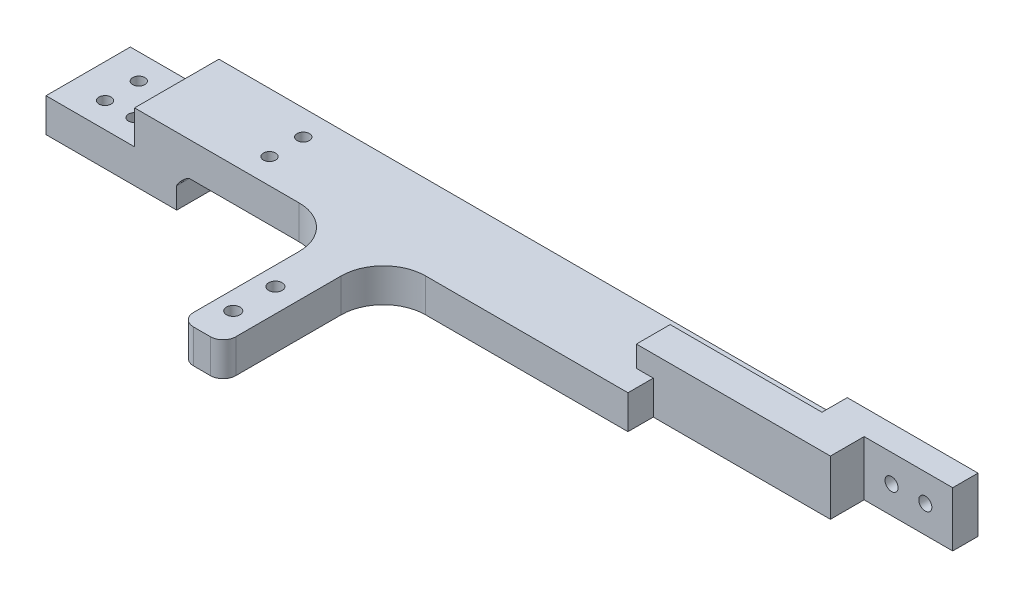
SolidWorks part; units mm, degrees
ref_plane "Front" through (0, 0, 0) normal (0, 0, 1) x (1, 0, 0)
ref_plane "Top" through (0, 0, 0) normal (0, 1, 0) x (1, 0, 0)
ref_plane "Right" through (0, 0, 0) normal (1, 0, 0) x (0, 0, -1)
sketch "Sketch1" plane through (0, 0, 0) normal (0, 1, 0) x (1, 0, 0)
  line L1 (0, 0) -> (300, 0)
  line L2 (0, 0) -> (0, -20)
  line L3 (0, -20) -> (300, -20)
  line L4 (300, 0) -> (300, -20)
  dimension "D1" = 20
  dimension "D2" = 300
extrude "Boss-Extrude1" add sketch "Sketch1" along normal blind 8
sketch "Sketch2" plane through (0, 0, 20) normal (0, 0, 1) x (1, 0, 0)
  line L0 (0, 8) -> (300, 8) construction
  line L1 (0, 0) -> (34, 0)
  line L2 (0, 0) -> (0, 8)
  line L3 (0, 8) -> (34, 8)
  line L4 (34, 0) -> (34, 8)
  line L5 (266, 8) -> (300, 8)
  line L6 (300, 0) -> (300, 8)
  line L7 (266, 0) -> (300, 0)
  line L8 (266, 0) -> (266, 8)
  dimension "D1" = 34
  dimension "D2" = 2
extrude "Boss-Extrude2" add sketch "Sketch2" along normal blind 9
sketch "Sketch3" plane through (0, 0, 0) normal (0, 0, -1) x (-1, 0, 0)
  line L0 (-300, 8) -> (0, 8) construction
  line L1 (0, 0) -> (-34, 0)
  line L2 (0, 0) -> (0, 8)
  line L3 (0, 8) -> (-34, 8)
  line L4 (-34, 0) -> (-34, 8)
  line L5 (-300, 0) -> (-300, 8)
  line L6 (-266, 8) -> (-300, 8)
  line L7 (-266, 0) -> (-266, 8)
  line L8 (-266, 0) -> (-300, 0)
  dimension "D1" = 34
  dimension "D2" = 2
extrude "Boss-Extrude3" add sketch "Sketch3" along normal blind 9
sketch "Sketch4" plane through (0, 8, 0) normal (0, 1, 0) x (1, 0, 0)
  line L0 (0, 9) -> (34, 9) construction
  line L1 (0, 9) -> (0, -29) construction
  circle A0 centre (4, 5) radius 1.45
  circle A1 centre (30, 5) radius 1.45
  circle A2 centre (30, -25) radius 1.45
  circle A3 centre (4, -25) radius 1.45
  circle A4 centre (296, -25) radius 1.45
  circle A5 centre (296, 5) radius 1.45
  circle A6 centre (270, -25) radius 1.45
  circle A7 centre (270, 5) radius 1.45
  dimension "D1" = 2.9
  dimension "D2" = 4
  dimension "D3" = 4
  dimension "D4" = 2
  dimension "D5" = 2
  dimension "D6" = 2
extrude "Cut-Extrude1" cut sketch "Sketch4" against normal through all
sketch "Sketch5" plane through (0, 0, 20) normal (0, 0, 1) x (1, 0, 0)
  line L0 (34, 8) -> (266, 8) construction
  line L1 (266, 0) -> (241, 0)
  line L2 (266, 0) -> (266, 8)
  line L3 (266, 8) -> (241, 8)
  line L4 (241, 0) -> (241, 8)
  dimension "D1" = 25
extrude "Boss-Extrude4" add sketch "Sketch5" along normal blind 17
sketch "Sketch6" plane through (0, 0, 0) normal (0, 0, -1) x (-1, 0, 0)
  line L0 (-266, 0) -> (-34, 0) construction
  line L1 (-266, 8) -> (-241, 8)
  line L2 (-266, 8) -> (-266, 0)
  line L3 (-266, 0) -> (-241, 0)
  line L4 (-241, 8) -> (-241, 0)
  dimension "D1" = 25
extrude "Boss-Extrude5" add sketch "Sketch6" along normal blind 17
sketch "Sketch12" plane through (0, 0, 37) normal (0, 0, 1) x (1, 0, 0)
  line L0 (241, 0) -> (266, 0) construction
  line L1 (241, 8) -> (249, 8)
  line L2 (241, 8) -> (241, 0)
  line L3 (241, 0) -> (249, 0)
  line L4 (249, 8) -> (249, 0)
  dimension "D1" = 8
extrude "Boss-Extrude7" add sketch "Sketch12" along normal blind 17
sketch "Sketch14" plane through (0, 0, 29) normal (0, 0, 1) x (1, 0, 0)
  line L0 (300, 8) -> (266, 8) construction
  line L1 (294.975, 8) -> (275, 8)
  line L2 (294.975, 8) -> (294.975, -5)
  line L3 (294.975, -5) -> (275, -4)
  line L4 (275, 8) -> (275, -4)
  line L7 (266, 8) -> (266, 0) construction
  dimension "D1" = 20
  dimension "D2" = 9
  dimension "D3" = 13
  dimension "D4" = 12
extrude "Boss-Extrude8" add sketch "Sketch14" along normal blind 12
sketch "Sketch15" plane through (294.975, 0, 0) normal (1, 0, 0) x (0, 0, -1)
  line L0 (-41, -5) -> (-41, 8) construction
  line L2 (-41, -5) -> (-29, -5) construction
  circle A0 centre (-35, 0) radius 1.6
  dimension "D1" = 3.2
  dimension "D2" = 6
  dimension "D3" = 5
extrude "Cut-Extrude7" cut sketch "Sketch15" against normal blind 20
sketch "Sketch16" plane through (0, 0, -9) normal (0, 0, -1) x (-1, 0, 0)
  line L0 (-266, 8) -> (-300, 8) construction
  line L1 (-295, 8) -> (-275, 8)
  line L2 (-295, 8) -> (-295, -5)
  line L3 (-295, -5) -> (-275, -5)
  line L4 (-275, 8) -> (-275, -5)
  line L6 (-266, 0) -> (-266, 8) construction
  dimension "D1" = 20
  dimension "D2" = 9
  dimension "D3" = 13
extrude "Boss-Extrude9" add sketch "Sketch16" along normal blind 12
sketch "Sketch17" plane through (295, 0, 0) normal (1, 0, 0) x (0, 0, -1)
  line L0 (21, -5) -> (9, -5) construction
  line L1 (21, 8) -> (21, -5) construction
  circle A0 centre (15, 0) radius 1.6
  dimension "D1" = 3.2
  dimension "D2" = 5
  dimension "D3" = 6
extrude "Cut-Extrude8" cut sketch "Sketch17" against normal blind 20
sketch "Sketch18" plane through (0, 0, -9) normal (0, 0, -1) x (-1, 0, 0)
  line L0 (0, 8) -> (-34, 8) construction
  line L1 (-25, 8) -> (-5, 8)
  line L2 (-25, 8) -> (-25, -5)
  line L3 (-25, -5) -> (-5, -5)
  line L4 (-5, 8) -> (-5, -5)
  line L6 (-34, 8) -> (-34, 0) construction
  dimension "D1" = 20
  dimension "D2" = 9
  dimension "D3" = 13
extrude "Boss-Extrude10" add sketch "Sketch18" along normal blind 12
sketch "Sketch19" plane through (5, 0, 0) normal (-1, 0, 0) x (0, 0, 1)
  line L0 (-21, -5) -> (-21, 8) construction
  line L2 (-21, -5) -> (-9, -5) construction
  circle A0 centre (-15, 0) radius 1.6
  dimension "D1" = 3.2
  dimension "D2" = 6
  dimension "D3" = 5
extrude "Cut-Extrude9" cut sketch "Sketch19" against normal blind 20
sketch "Sketch20" plane through (0, 0, 29) normal (0, 0, 1) x (1, 0, 0)
  line L0 (34, 8) -> (0, 8) construction
  line L1 (5, 8) -> (25, 8)
  line L2 (5, 8) -> (5, -5)
  line L3 (5, -5) -> (25, -5)
  line L4 (25, 8) -> (25, -5)
  line L6 (34, 0) -> (34, 8) construction
  dimension "D1" = 20
  dimension "D2" = 9
  dimension "D3" = 13
extrude "Boss-Extrude11" add sketch "Sketch20" along normal blind 12
sketch "Sketch21" plane through (5, 0, 0) normal (-1, 0, 0) x (0, 0, 1)
  line L0 (41, 8) -> (41, -5) construction
  line L1 (41, -5) -> (29, -5) construction
  circle A0 centre (35, 0) radius 1.6
  dimension "D1" = 3.2
  dimension "D2" = 6
  dimension "D3" = 5
extrude "Cut-Extrude10" cut sketch "Sketch21" against normal blind 20
sketch "Sketch22" plane through (0, 8, 0) normal (0, 1, 0) x (1, 0, 0)
  line L0 (241, 17) -> (241, 0) construction
  line L1 (259, 9) -> (249, 9)
  line L2 (259, 9) -> (259, -29)
  line L3 (259, -29) -> (249, -29)
  line L4 (249, 9) -> (249, -29)
  line L5 (241, 17) -> (266, 17) construction
  line L6 (266, -37) -> (249, -37) construction
  dimension "D1" = 8
  dimension "D2" = 10
  dimension "D3" = 8
  dimension "D4" = 8
extrude "Cut-Extrude11" cut sketch "Sketch22" against normal through all
sketch "Sketch23" plane through (0, 0, 0) normal (0, -1, 0) x (-1, 0, 0)
  line L0 (-259, -29) -> (-259, 9) construction
  line L1 (-259, -19) -> (-267, -19)
  line L2 (-259, -19) -> (-259, -1)
  line L3 (-259, -1) -> (-267, -1)
  line L4 (-267, -19) -> (-267, -1)
  line L5 (-249, -29) -> (-259, -29) construction
  dimension "D1" = 8
  dimension "D2" = 10
  dimension "D3" = 10
extrude "Cut-Extrude12" cut sketch "Sketch23" against normal blind 4
sketch "Sketch24" plane through (259, 0, 0) normal (-1, 0, 0) x (0, 0, 1)
  line L0 (-9, 0) -> (-9, 8)
  line L1 (-9, 8) -> (-1, 8)
  line L2 (29, 8) -> (-9, 8) construction
  line L3 (-1, 8) -> (-9, 0)
  line L4 (29, 0) -> (29, 8)
  line L5 (29, 8) -> (21, 8)
  line L6 (21, 8) -> (29, 0)
  dimension "D1" = 8
  dimension "D2" = 8
extrude "Boss-Extrude12" add sketch "Sketch24" along normal blind 10
sketch "Sketch25" plane through (267, 0, 0) normal (-1, 0, 0) x (0, 0, 1)
  line L0 (19, 0) -> (19, 4)
  line L1 (19, 4) -> (15, 4)
  line L2 (1, 4) -> (19, 4) construction
  line L3 (15, 4) -> (19, 0)
  line L4 (1, 4) -> (5, 4)
  line L5 (5, 4) -> (1, 0)
  line L6 (1, 0) -> (1, 4)
  dimension "D1" = 4
  dimension "D2" = 4
extrude "Boss-Extrude13" add sketch "Sketch25" along normal blind 8
sketch "Sketch26" plane through (0, 8, 0) normal (0, 1, 0) x (1, 0, 0)
  line L0 (249, 1) -> (249, -21) construction
  line L1 (241, -54) -> (249, -54)
  line L2 (241, -54) -> (241, -6)
  line L3 (241, -6) -> (249, -6)
  line L4 (249, -54) -> (249, -6)
  dimension "D1" = 48
extrude "Boss-Extrude14" add sketch "Sketch26" along normal blind 14
sketch "Sketch27" plane through (0, 8, 0) normal (0, 1, 0) x (1, 0, 0)
  line L0 (249, -21) -> (259, -21) construction
  line L1 (249, -37) -> (257, -37)
  line L2 (249, -37) -> (249, -21)
  line L3 (249, -21) -> (257, -21)
  line L4 (257, -37) -> (257, -21)
  dimension "D1" = 8
extrude "Boss-Extrude15" add sketch "Sketch27" along normal blind 14
sketch "Sketch28" plane through (0, 0, 0) normal (0, -1, 0) x (1, 0, 0)
  line L0 (249, -9) -> (249, 29) construction
  line L1 (241, 54) -> (249, 54)
  line L2 (241, 54) -> (241, 14)
  line L3 (241, 14) -> (249, 14)
  line L4 (249, 54) -> (249, 14)
  dimension "D1" = 40
extrude "Cut-Extrude13" cut sketch "Sketch28" against normal blind 14
sketch "Sketch30" plane through (257, 0, 0) normal (1, 0, 0) x (0, 0, -1)
  line L0 (-37, 22) -> (-21, 22) construction
  line L1 (-21, 22) -> (-37, 22)
  line L2 (-21, 22) -> (-21, 8)
  line L3 (-21, 8) -> (-37, 8)
  line L4 (-37, 22) -> (-37, 8)
extrude "Boss-Extrude16" add sketch "Sketch30" along normal blind 9
sketch "Sketch31" plane through (0, 0, 0) normal (0, -1, 0) x (-1, 0, 0)
  line L1 (-249, -37) -> (-266, -37)
  line L2 (-249, -37) -> (-249, -29)
  line L3 (-249, -29) -> (-266, -29)
  line L4 (-266, -37) -> (-266, -29)
extrude "Cut-Extrude14" cut sketch "Sketch31" against normal blind 5
sketch "Sketch32" plane through (266, 0, 0) normal (1, 0, 0) x (0, 0, -1)
  line L0 (-37, 5) -> (-37, 22) construction
  line L1 (-21, 22) -> (-37, 22)
  line L2 (-21, 22) -> (-21, 13)
  line L3 (-21, 13) -> (-37, 13)
  line L4 (-37, 22) -> (-37, 13)
  dimension "D1" = 9
extrude "Cut-Extrude15" cut sketch "Sketch32" against normal blind 9
sketch "Sketch33" plane through (249, 0, 0) normal (-1, 0, 0) x (0, 0, 1)
  line L0 (29, 5) -> (24, 5)
  line L1 (21, 8) -> (29, 0) construction
  line L2 (24, 5) -> (29, 0)
  line L3 (29, 0) -> (29, 5)
extrude "Cut-Extrude16" cut sketch "Sketch33" against normal blind 10
sketch "Sketch34" plane through (0, 0, 29) normal (0, 0, 1) x (1, 0, 0)
  line L1 (266, 5) -> (259, 5)
  line L2 (266, 5) -> (266, 0)
  line L3 (266, 0) -> (259, 0)
  line L4 (259, 5) -> (259, 0)
extrude "Cut-Extrude17" cut sketch "Sketch34" against normal blind 5
sketch "Sketch35" plane through (0, 0, 21) normal (0, 0, -1) x (-1, 0, 0)
  line L0 (-249, 8) -> (-259, 8) construction
  line L1 (-259, 8) -> (-266, 8)
  line L2 (-259, 8) -> (-259, 13)
  line L3 (-259, 13) -> (-266, 13)
  line L4 (-266, 8) -> (-266, 13)
  line L5 (-266, 8) -> (-259, 8) construction
  line L6 (-266, 8) -> (-266, 13) construction
extrude "Boss-Extrude17" add sketch "Sketch35" along normal blind 5
sketch "Sketch36" plane through (0, 22, 0) normal (0, 1, 0) x (1, 0, 0)
  line L0 (241, -54) -> (249, -54) construction
  line L1 (249, -54) -> (249, -37) construction
  circle A0 centre (245, -50) radius 1.7
  circle A1 centre (245, -18) radius 1.7
  dimension "D1" = 3.4
  dimension "D2" = 4
  dimension "D3" = 4
  dimension "D4" = 2
extrude "Cut-Extrude18" cut sketch "Sketch36" against normal through all
sketch "Sketch37" plane through (0, 8, 0) normal (0, 1, 0) x (1, 0, 0)
  line L0 (241, -6) -> (171, -6)
  line L1 (241, -6) -> (241, -14) construction
  line L2 (241, -6) -> (241, -14)
  line L3 (241, -14) -> (241, -20) construction
  line L4 (241, -14) -> (171, -14)
  line L5 (171, -14) -> (171, -6)
  dimension "D1" = 70
extrude "Boss-Extrude18" add sketch "Sketch37" along normal blind 5
sketch "Sketch39" plane through (0, 8, 0) normal (0, 1, 0) x (1, 0, 0)
  line L0 (34, -20) -> (241, -20) construction
  line L1 (241, -14) -> (175, -14)
  line L2 (241, -14) -> (241, -20)
  line L3 (241, -20) -> (175, -20)
  line L4 (175, -14) -> (175, -20)
  dimension "D1" = 66
extrude "Cut-Extrude19" cut sketch "Sketch39" against normal through all
sketch "Sketch40" plane through (0, 8, 0) normal (0, 1, 0) x (1, 0, 0)
  line L1 (5, 9) -> (25, 9)
  line L2 (5, 9) -> (5, 21)
  line L3 (5, 21) -> (25, 21)
  line L4 (25, 9) -> (25, 21)
extrude "Boss-Extrude19" add sketch "Sketch40" along normal blind 10
sketch "Sketch41" plane through (0, 18, 0) normal (0, 1, 0) x (1, 0, 0)
  line L0 (25, 21) -> (5, 21) construction
  line L1 (25, 21) -> (-3, 21)
  line L2 (25, 21) -> (25, 9)
  line L3 (25, 9) -> (-3, 9)
  line L4 (-3, 21) -> (-3, 9)
  line L5 (5, 9) -> (25, 9) construction
  line L6 (25, 9) -> (25, 21) construction
  line L7 (5, 21) -> (5, 9) construction
  dimension "D1" = 28
  dimension "D2" = 20
extrude "Boss-Extrude20" add sketch "Sketch41" along normal blind 5 and the other way blind 5
sketch "Sketch42" plane through (-3, 0, 0) normal (-1, 0, 0) x (0, 0, 1)
  line L0 (-21, 23) -> (-9, 23) construction
  line L1 (-9, 13) -> (-9, 23) construction
  circle A0 centre (-14, 18) radius 1.5
  dimension "D1" = 3
  dimension "D2" = 5
  dimension "D3" = 5
extrude "Cut-Extrude20" cut sketch "Sketch42" against normal blind 15
sketch "Sketch43" plane through (0, 8, 0) normal (0, 1, 0) x (1, 0, 0)
  line L1 (5, -41) -> (25, -41)
  line L2 (5, -41) -> (5, -29)
  line L3 (5, -29) -> (25, -29)
  line L4 (25, -41) -> (25, -29)
extrude "Boss-Extrude21" add sketch "Sketch43" along normal blind 10
sketch "Sketch44" plane through (0, 18, 0) normal (0, 1, 0) x (1, 0, 0)
  line L0 (25, -29) -> (5, -29) construction
  line L1 (-3, -29) -> (25, -29)
  line L2 (-3, -29) -> (-3, -41)
  line L3 (-3, -41) -> (25, -41)
  line L4 (25, -29) -> (25, -41)
  line L5 (5, -41) -> (25, -41) construction
  line L6 (25, -41) -> (25, -29) construction
  line L7 (5, -29) -> (5, -41) construction
  dimension "D1" = 28
  dimension "D2" = 20
extrude "Boss-Extrude22" add sketch "Sketch44" along normal blind 5 and the other way blind 5
sketch "Sketch45" plane through (-3, 0, 0) normal (-1, 0, 0) x (0, 0, 1)
  line L0 (29, 23) -> (41, 23) construction
  line L1 (41, 13) -> (41, 23) construction
  circle A0 centre (36, 18) radius 1.5
  dimension "D1" = 3
  dimension "D2" = 5
  dimension "D3" = 5
extrude "Cut-Extrude21" cut sketch "Sketch45" against normal blind 15
sketch "Sketch46" plane through (0, 8, 0) normal (0, 1, 0) x (1, 0, 0)
  line L1 (295, 9) -> (275, 9)
  line L2 (295, 9) -> (295, 21)
  line L3 (295, 21) -> (275, 21)
  line L4 (275, 9) -> (275, 21)
  line L5 (294.975, -41) -> (275, -41)
  line L6 (294.975, -41) -> (294.975, -29)
  line L7 (294.975, -29) -> (275, -29)
  line L8 (275, -41) -> (275, -29)
extrude "Boss-Extrude23" add sketch "Sketch46" along normal blind 10
sketch "Sketch47" plane through (0, 18, 0) normal (0, 1, 0) x (1, 0, 0)
  line L0 (295, 21) -> (275, 21) construction
  line L1 (275, 21) -> (303, 21)
  line L2 (275, 21) -> (275, 9)
  line L3 (275, 9) -> (303, 9)
  line L4 (303, 21) -> (303, 9)
  line L5 (275, 9) -> (295, 9) construction
  line L6 (294.975, -29) -> (275, -29) construction
  line L7 (274.975, -29) -> (303, -29)
  line L8 (274.975, -29) -> (274.975, -41)
  line L9 (274.975, -41) -> (303, -41)
  line L10 (303, -29) -> (303, -41)
  line L11 (275, -41) -> (294.975, -41) construction
  line L12 (275, 21) -> (275, 9) construction
  line L13 (295, 9) -> (295, 21) construction
  line L14 (275, -29) -> (275, -41) construction
  line L15 (294.975, -41) -> (294.975, -29) construction
  dimension "D1" = 28
  dimension "D2" = 20
  dimension "D3" = 28
  dimension "D4" = 20
extrude "Boss-Extrude24" add sketch "Sketch47" along normal blind 5 and the other way blind 5
sketch "Sketch48" plane through (303, 0, 0) normal (1, 0, 0) x (0, 0, -1)
  line L2 (-41, 13) -> (-41, 23) construction
  line L3 (21, 13) -> (21, 23) construction
  line L4 (9, 23) -> (21, 23) construction
  line L5 (-41, 23) -> (-29, 23) construction
  circle A0 centre (16, 18) radius 1.5
  circle A1 centre (-36, 18) radius 1.5
  dimension "D1" = 3
  dimension "D2" = 3
  dimension "D3" = 5
  dimension "D4" = 5
  dimension "D5" = 5
  dimension "D6" = 5
extrude "Cut-Extrude22" cut sketch "Sketch48" against normal blind 15
fillet "Fillet1" radius 5 4 edges at (294.975, 13, 35) (295, 13, -15) (5, 13, 35) (5, 13, -15)
fillet "Fillet2" radius 2.5 4 edges at (15, 8, -9) (15, 8, 29) (284.9875, 8, 29) (285, 8, -9)
fillet "Fillet3" radius 3 8 edges at (284.9875, -4.5, 41) (284.9875, -4.5, 29) (285, -5, -21) (285, -5, -9) (15, -5, -21) (15, -5, -9) (15, -5, 29) (15, -5, 41)
fillet "Fillet4" radius 3 8 edges at (11, 23, -21) (11, 23, -9) (11, 23, 29) (11, 23, 41) (289, 23, -9) (289, 23, -21) (288.9875, 23, 41) (288.9875, 23, 29)
sketch "Sketch49" plane through (0, 8, 0) normal (0, 1, 0) x (1, 0, 0)
  line L0 (241, 0) -> (34, 0) construction
  line L1 (34, -20) -> (175, -20) construction
  line L2 (0, 9) -> (0, -29) construction
  circle A0 centre (84, -6) radius 1.45
  circle A1 centre (84, -14) radius 1.45
  dimension "D1" = 2.9
  dimension "D2" = 2.9
  dimension "D3" = 6
  dimension "D4" = 6
  dimension "D5" = 84
  dimension "D6" = 84
extrude "Cut-Extrude23" cut sketch "Sketch49" against normal through all
sketch "Sketch50" plane through (-3, 0, 0) normal (-1, 0, 0) x (0, 0, 1)
  line L1 (-34.8128, -21.6618) -> (62.794, -21.6618)
  line L2 (-34.8128, -21.6618) -> (-34.8128, 36.6095)
  line L3 (-34.8128, 36.6095) -> (62.794, 36.6095)
  line L4 (62.794, -21.6618) -> (62.794, 36.6095)
extrude "Cut-Extrude24" cut sketch "Sketch50" against normal blind 40
sketch "Sketch51" plane through (303, 0, 0) normal (1, 0, 0) x (0, 0, -1)
  line L1 (33.5869, 36.8102) -> (-70.4933, 36.8102)
  line L2 (33.5869, 36.8102) -> (33.5869, -31.9678)
  line L3 (33.5869, -31.9678) -> (-70.4933, -31.9678)
  line L4 (-70.4933, 36.8102) -> (-70.4933, -31.9678)
extrude "Cut-Extrude25" cut sketch "Sketch51" against normal blind 65
sketch "Sketch54" plane through (238, 0, 0) normal (1, 0, 0) x (0, 0, -1)
  line L1 (-6, 13) -> (-14, 13)
  line L2 (-6, 13) -> (-6, 0)
  line L3 (-6, 0) -> (-14, 0)
  line L4 (-14, 13) -> (-14, 0)
extrude "Cut-Extrude26" cut sketch "Sketch54" against normal blind 21
sketch "Sketch55" plane through (0, 8, 0) normal (0, 1, 0) x (1, 0, 0)
  line L0 (238, 0) -> (37, 0) construction
  line L1 (238, -6) -> (207, -6)
  line L2 (238, -6) -> (238, 0)
  line L3 (238, 0) -> (207, 0)
  line L4 (207, -6) -> (207, 0)
  dimension "D1" = 31
extrude "Boss-Extrude26" add sketch "Sketch55" along normal blind 5
sketch "Sketch56" plane through (0, 0, 6) normal (0, 0, 1) x (1, 0, 0)
  line L0 (217, 0) -> (217, 13) construction
  circle A0 centre (231.5, 6.5) radius 1.55
  circle A1 centre (223.5, 6.5) radius 1.55
  dimension "D1" = 3.1
  dimension "D2" = 3.1
  dimension "D3" = 8
  dimension "D4" = 6.5
extrude "Cut-Extrude27" cut sketch "Sketch56" against normal through all
sketch "Sketch57" plane through (0, 0, 0) normal (0, -1, 0) x (-1, 0, 0)
  line L0 (-238, 0) -> (-37, 0) construction
  line L1 (-37, -20) -> (-68, -20)
  line L2 (-37, -20) -> (-37, 0)
  line L3 (-37, 0) -> (-68, 0)
  line L4 (-68, -20) -> (-68, 0)
  dimension "D1" = 31
extrude "Boss-Extrude27" add sketch "Sketch57" along normal blind 8
sketch "Sketch58" plane through (0, 8, 0) normal (0, 1, 0) x (1, 0, 0)
  line L0 (37, -20) -> (175, -20) construction
  line L1 (37, 0) -> (58, 0)
  line L2 (37, 0) -> (37, -20)
  line L3 (37, -20) -> (58, -20)
  line L4 (58, 0) -> (58, -20)
  dimension "D1" = 21
extrude "Cut-Extrude28" cut sketch "Sketch58" against normal blind 8
sketch "Sketch59" plane through (0, 0, 0) normal (0, 1, 0) x (1, 0, 0)
  line L1 (58, 0) -> (37, 0) construction
  line L2 (37, -20) -> (58, -20) construction
  line L3 (58, -20) -> (58, 0) construction
  circle A0 centre (52, -6) radius 1.45
  circle A1 centre (45, -6) radius 1.45
  circle A2 centre (45, -14) radius 1.45
  circle A3 centre (52, -14) radius 1.45
  dimension "D2" = 2.9
  dimension "D3" = 2.9
  dimension "D4" = 2.9
  dimension "D1" = 2.9
  dimension "D5" = 6
  dimension "D6" = 6
  dimension "D7" = 6
  dimension "D8" = 6
  dimension "D9" = 7
  dimension "D10" = 7
extrude "Cut-Extrude29" cut sketch "Sketch59" against normal through all
sketch "Sketch60" plane through (0, 0, 20) normal (0, 0, 1) x (1, 0, 0)
  line L0 (68, 0) -> (175, 0) construction
  line L1 (107, 0) -> (117, 0)
  line L2 (107, 0) -> (107, 8)
  line L3 (107, 8) -> (117, 8)
  line L4 (117, 0) -> (117, 8)
  line L5 (58, 8) -> (175, 8) construction
  line L6 (58, 0) -> (58, 8) construction
  dimension "D1" = 10
  dimension "D2" = 49
extrude "Boss-Extrude28" add sketch "Sketch60" along normal blind 38
sketch "Sketch61" plane through (0, 8, 0) normal (0, 1, 0) x (1, 0, 0)
  line L0 (107, -58) -> (107, -20) construction
  line L1 (58, -20) -> (107, -20) construction
  circle A0 centre (111.4, -50) radius 1.6
  circle A1 centre (111.4, -40) radius 1.6
  dimension "D1" = 3.2
  dimension "D2" = 3.2
  dimension "D3" = 10
  dimension "D4" = 4.4
  dimension "D5" = 4.4
  dimension "D6" = 20
extrude "Cut-Extrude30" cut sketch "Sketch61" against normal through all
fillet "Fillet5" radius 10 2 edges at (107, 4, 20) (117, 4, 20)
fillet "Fillet6" radius 3 1 edges at (68, 0, 10) conic rho 0.15
fillet "Fillet7" radius 3 2 edges at (117, 4, 58) (107, 4, 58)
